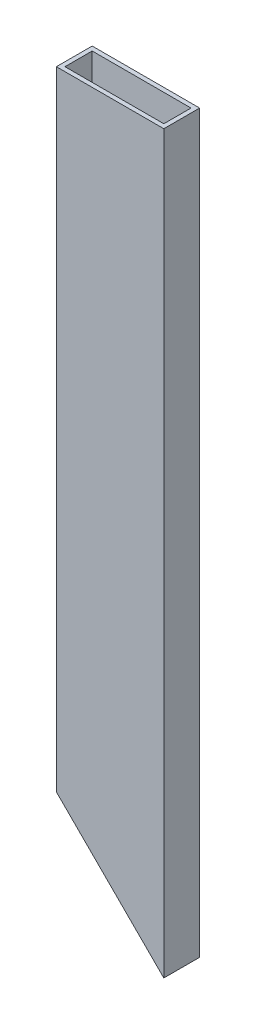
SolidWorks part; units mm, degrees
note: '?' marks a value the reader was unsure of.
material "A500"
ref_plane "Front Plane" through (0, 0, 0) normal (0, 0, 1) x (1, 0, 0)
ref_plane "Top Plane" through (0, 0, 0) normal (0, 1, 0) x (1, 0, 0)
ref_plane "Right Plane" through (0, 0, 0) normal (1, 0, 0) x (0, 0, -1)
sketch "Sketch1" plane through (0, 0, 0) normal (0, 1, 0) x (1, 0, 0)
  line L0 (0, 9.652) -> (0, 12.7) construction
  line L1 (-38.1, 12.7) -> (38.1, 12.7)
  line L2 (-38.1, 12.7) -> (-38.1, -12.7)
  line L3 (-38.1, -12.7) -> (38.1, -12.7)
  line L4 (38.1, 12.7) -> (38.1, -12.7)
  line L5 (-35.052, 9.652) -> (35.052, 9.652)
  line L6 (-35.052, 9.652) -> (-35.052, -9.652)
  line L7 (-35.052, -9.652) -> (35.052, -9.652)
  line L8 (35.052, 9.652) -> (35.052, -9.652)
  line L9 (35.052, 0) -> (38.1, 0) construction
  line L10 (0, -9.652) -> (0, -12.7) construction
  line L11 (-35.052, 0) -> (-38.1, 0) construction
  line L12 (0, 9.652) -> (0, 0) construction
  line L13 (0, 0) -> (-35.052, 0) construction
  dimension "D1" = 76.2
  dimension "D2" = 25.4
  dimension "D3" = 3.048
extrude "Boss-Extrude1" add sketch "Sketch1" along normal up to vertex (445.4 mm away)
ref_plane "Plane1" through (0, 0, 0) normal (0, 0, 1) x (1, 0, 0)
sketch "Sketch2" plane through (0, 0, 0) normal (0, 0, 1) x (1, 0, 0)
  line L0 (0, 0) -> (0, 445.4) construction
  line L1 (-38.1, 445.4) -> (38.1, 445.4) construction
  line L2 (0, 222.7) -> (-38.1, 222.7) construction
  line L3 (-38.1, 445.4) -> (-38.1, 0) construction
  line L4 (0, 222.7) -> (38.1, 222.7) construction
  line L5 (38.1, 445.4) -> (38.1, 0) construction
ref_axis "Axis1" through (0, 445.4, 0) along (0, -1, 0)?
sketch "Sketch3" plane through (0, 0, 0) normal (0, -1, 0) x (1, 0, 0)
  line L0 (38.1, 12.7) -> (38.1, -12.7) construction
  line L1 (35.052, 9.652) -> (35.052, -9.652) construction
  line L2 (-35.052, 9.652) -> (35.052, 9.652) construction
  line L3 (-35.052, -9.652) -> (-35.052, 9.652) construction
  line L4 (35.052, -9.652) -> (-35.052, -9.652) construction
  line L5 (38.1, -12.7) -> (-38.1, -12.7) construction
  line L6 (-38.1, 12.7) -> (38.1, 12.7) construction
  line L7 (-38.1, -12.7) -> (-38.1, 12.7) construction
  line L8 (38.1, 12.7) -> (38.1, -12.7)
  line L9 (35.052, 9.652) -> (35.052, -9.652)
  line L10 (-35.052, 9.652) -> (35.052, 9.652)
  line L11 (-35.052, -9.652) -> (-35.052, 9.652)
  line L12 (35.052, -9.652) -> (-35.052, -9.652)
  line L13 (38.1, -12.7) -> (-38.1, -12.7)
  line L14 (-38.1, 12.7) -> (38.1, 12.7)
  line L15 (-38.1, -12.7) -> (-38.1, 12.7)
extrude "Boss-Extrude2" add sketch "Sketch3" along normal blind 38.1
sketch "Sketch4" plane through (0, 445.4, 0) normal (0, 1, 0) x (1, 0, 0)
  line L0 (35.052, -9.652) -> (35.052, 9.652) construction
  line L1 (35.052, 9.652) -> (-35.052, 9.652) construction
  line L2 (-35.052, -9.652) -> (35.052, -9.652) construction
  line L3 (-35.052, 9.652) -> (-35.052, -9.652) construction
  line L4 (-38.1, 12.7) -> (-38.1, -12.7)
  line L5 (-38.1, -12.7) -> (38.1, -12.7)
  line L6 (38.1, -12.7) -> (38.1, 12.7)
  line L7 (38.1, 12.7) -> (-38.1, 12.7)
  line L8 (-38.1, 12.7) -> (-38.1, -12.7)
  line L9 (-38.1, -12.7) -> (38.1, -12.7)
  line L10 (38.1, -12.7) -> (38.1, 12.7)
  line L11 (38.1, 12.7) -> (-38.1, 12.7)
  line L12 (35.052, -9.652) -> (35.052, 9.652)
  line L13 (35.052, 9.652) -> (-35.052, 9.652)
  line L14 (-35.052, -9.652) -> (35.052, -9.652)
  line L15 (-35.052, 9.652) -> (-35.052, -9.652)
  dimension "D1" = 0
extrude "Boss-Extrude3" add sketch "Sketch4" along normal blind 38.1
sketch "Sketch5" plane through (-500, 0, 0) normal (0, 0, -1) x (1, 0, 0)
  line L0 (607.1561, 107.1561) -> (437.0114, -62.9886)
  line L1 (474.6, 0) -> (437.0114, -62.9886) construction
  line L2 (0, 0) -> (500, 0) construction
  line L3 (437.0114, -62.9886) -> (500, -25.4) construction
  line L4 (500, 0) -> (500, -445.4) construction
  line L5 (607.1561, 107.1561) -> (437.0114, 107.1561)
  line L6 (437.0114, 107.1561) -> (437.0114, -62.9886)
  dimension "D1" = 25.4
  dimension "D2" = 25.4
extrude "Cut-Extrude1" cut sketch "Sketch5" against normal through all both and the other way through all
equation "\"halfMainWidthOfTubing\"= (\"tubeMainWidth\"/2)"
equation "\"tubeMainWidth\"= 76.2mm"
equation "\"tubeSecondWidth\"= 25.4mm"
equation "\"tubeThickness\"= 3.048mm"
equation "\"D1@Sketch1\"=\"tubeMainWidth\""
equation "\"D2@Sketch1\"=\"tubeSecondWidth\""
equation "\"D3@Sketch1\"=\"tubeThickness\""
equation "\"D1@Boss-Extrude2\"=\"halfMainWidthOfTubing\""
equation "\"D1@Boss-Extrude3\"=\"halfMainWidthOfTubing\""
